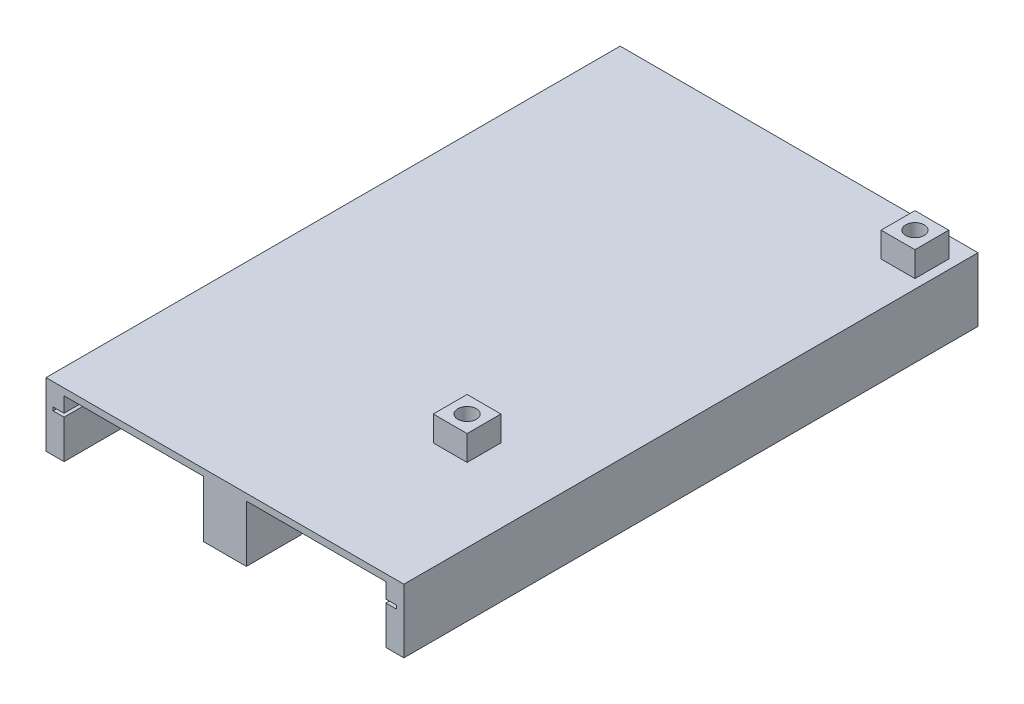
SolidWorks part; units mm, degrees
material "PLA"
ref_plane "Спереди" through (0, 0, 0) normal (0, 0, 1) x (1, 0, 0)
ref_plane "Сверху" through (0, 0, 0) normal (0, 1, 0) x (1, 0, 0)
ref_plane "Справа" through (0, 0, 0) normal (1, 0, 0) x (0, 0, -1)
sketch "Эскиз1" plane through (0, 0, 0) normal (0, 1, 0) x (1, 0, 0)
  line L0 (0, 0) -> (-4740.9496, 0) construction
  line L1 (0, 0) -> (0, -4740.9496) construction
  line L2 (35.675, 63.65) -> (39.675, 63.65)
  line L3 (-35.675, -63.65) -> (-39.675, -63.65)
  line L4 (-35.675, -63.65) -> (-35.675, 63.65)
  line L5 (-35.675, 63.65) -> (-39.675, 63.65)
  line L6 (-39.675, -63.65) -> (-39.675, 63.65)
  line L7 (-35.675, -63.65) -> (-39.675, 63.65) construction
  line L8 (-35.675, 63.65) -> (-39.675, -63.65) construction
  line L9 (39.675, -63.65) -> (39.675, 63.65)
  line L10 (35.675, -63.65) -> (39.675, -63.65)
  line L11 (35.675, -63.65) -> (35.675, 63.65)
  line L12 (35.675, 63.65) -> (39.675, -63.65) construction
  line L13 (35.675, -63.65) -> (39.675, 63.65) construction
  point P5 (-37.675, 0)
  point P14 (37.675, 0)
  dimension "D1" = 4
  dimension "D2" = 127.3
  dimension "D3" = 71.35
extrude "Бобышка-Вытянуть1" add sketch "Эскиз1" along normal blind 12.65
sketch "Эскиз2" plane through (0, 12.65, 0) normal (0, 1, 0) x (1, 0, 0)
  line L1 (39.675, 63.65) -> (-39.675, 63.65)
  line L2 (39.675, 63.65) -> (39.675, -63.65)
  line L3 (39.675, -63.65) -> (-39.675, -63.65)
  line L4 (-39.675, 63.65) -> (-39.675, -63.65)
extrude "Бобышка-Вытянуть2" add sketch "Эскиз2" along normal blind 1.5
sketch "Эскиз3" plane through (0, 0, -63.65) normal (0, 0, -1) x (-1, 0, 0)
  line L0 (0, 0) -> (0, 50000) construction
  line L1 (-35.675, 12.65) -> (-35.675, 0) construction
  line L2 (-35.675, 9.3) -> (-38.075, 9.3)
  line L3 (-35.675, 9.3) -> (-35.675, 8.55)
  line L4 (-35.675, 8.55) -> (-38.075, 8.55)
  line L5 (-38.075, 9.3) -> (-38.075, 8.55)
  line L6 (35.675, 8.55) -> (38.075, 8.55)
  line L7 (38.075, 9.3) -> (38.075, 8.55)
  line L8 (35.675, 9.3) -> (38.075, 9.3)
  line L9 (35.675, 9.3) -> (35.675, 8.55)
  line L10 (-39.675, 0) -> (-35.675, 0) construction
  dimension "D1" = 2.4
  dimension "D2" = 0.75
  dimension "D3" = 8.55
extrude "Вырез-Вытянуть1" cut sketch "Эскиз3" against normal through all from offset 1.5 offset against normal yes
sketch "Эскиз4" plane through (0, 12.65, 0) normal (0, -1, 0) x (1, 0, 0)
  line L0 (35.675, -63.65) -> (35.675, 63.65) construction
  line L1 (-35.675, -63.65) -> (35.675, -63.65)
  line L2 (-35.675, -63.65) -> (-35.675, -62.15)
  line L3 (-35.675, -62.15) -> (35.675, -62.15)
  line L4 (35.675, -63.65) -> (35.675, -62.15)
  dimension "D1" = 1.5
extrude "Бобышка-Вытянуть3" add sketch "Эскиз4" along normal up to surface (12.65 mm away) up to face at (37.675, 0, 0)
sketch "Эскиз6" plane through (0, 12.65, 0) normal (0, -1, 0) x (1, 0, 0)
  line L0 (35.675, -62.15) -> (35.675, 63.65) construction
  line L1 (32.325, -52.35) -> (24.825, -52.35)
  line L2 (32.325, -52.35) -> (32.325, -62.15)
  line L3 (32.325, -59.85) -> (24.825, -59.85) construction
  line L4 (24.825, -52.35) -> (24.825, -62.15)
  line L5 (32.325, -52.35) -> (24.825, -59.85) construction
  line L6 (32.325, -59.85) -> (24.825, -52.35) construction
  line L7 (35.675, -62.15) -> (-35.675, -62.15) construction
  line L8 (32.325, -62.15) -> (24.825, -62.15)
  circle A0 centre (28.575, -56.1) radius 2.1 construction
  point P0 (28.575, -56.1)
  dimension "D3" = 4.2
  dimension "D4" = 1.65
  dimension "D5" = 1.65
  dimension "D1" = 7.1
  dimension "D2" = 6.05
extrude "Бобышка-Вытянуть5" add sketch "Эскиз6" along normal blind 9.6
sketch "Эскиз7" plane through (0, 3.05, 0) normal (0, -1, 0) x (1, 0, 0)
  line L0 (24.825, -52.35) -> (32.325, -59.85) construction
  line L1 (32.325, -52.35) -> (24.825, -59.85) construction
  line L2 (32.325, -62.15) -> (32.325, -52.35) construction
  line L3 (24.825, -52.35) -> (24.825, -62.15) construction
  circle A0 centre (28.575, -56.1) radius 2.05
  dimension "D1" = 4.1
extrude "Вырез-Вытянуть2" cut sketch "Эскиз7" against normal blind 4.5
sketch "Эскиз8" plane through (0, 0, 0) normal (0, -1, 0) x (1, 0, 0)
  line L0 (-35.675, 63.65) -> (-35.675, -62.15) construction
  line L1 (-35.675, 38.05) -> (-38.075, 38.05)
  line L2 (-35.675, 38.05) -> (-35.675, 32.2)
  line L3 (-35.675, 32.2) -> (-38.075, 32.2)
  line L4 (-38.075, 38.05) -> (-38.075, 32.2)
  line L5 (0, 0) -> (0, 50000) construction
  line L6 (-35.675, -16.55) -> (-38.075, -16.55)
  line L7 (-35.675, -16.55) -> (-35.675, -22.4)
  line L8 (-35.675, -22.4) -> (-38.075, -22.4)
  line L9 (-38.075, -16.55) -> (-38.075, -22.4)
  line L10 (-39.675, 63.65) -> (-35.675, 63.65) construction
  line L11 (35.675, -22.4) -> (38.075, -22.4)
  line L12 (38.075, -16.55) -> (38.075, -22.4)
  line L13 (35.675, -16.55) -> (38.075, -16.55)
  line L14 (35.675, -16.55) -> (35.675, -22.4)
  line L15 (35.675, 32.2) -> (38.075, 32.2)
  line L16 (38.075, 38.05) -> (38.075, 32.2)
  line L17 (35.675, 38.05) -> (38.075, 38.05)
  line L18 (35.675, 38.05) -> (35.675, 32.2)
  line L19 (39.675, -63.65) -> (-39.675, -63.65) construction
  point P26 (0, -63.65)
  dimension "D1" = 2.4
  dimension "D2" = 5.85
  dimension "D3" = 48.75
  dimension "D4" = 25.6
extrude "Вырез-Вытянуть3" cut sketch "Эскиз8" against normal up to surface (8.55 mm away) up to face at (-36.875, 8.55, 0.75)
sketch "Эскиз10" plane through (0, 12.65, 0) normal (0, -1, 0) x (1, 0, 0)
  line L0 (-35.675, 63.65) -> (-35.675, -62.15) construction
  line L1 (-25.275, -51.75) -> (-28.275, -51.75)
  line L2 (-25.275, -51.75) -> (-25.275, -57.7)
  line L3 (-25.275, -57.7) -> (-28.275, -57.7)
  line L4 (-28.275, -51.75) -> (-28.275, -57.7)
  line L5 (24.825, -62.15) -> (-35.675, -62.15) construction
  line L6 (35.675, -62.15) -> (-35.675, -62.15) construction
  line L8 (15.225, -51.75) -> (18.225, -51.75)
  line L9 (15.225, -51.75) -> (15.225, -57.7)
  line L10 (15.225, -57.7) -> (18.225, -57.7)
  line L11 (18.225, -51.75) -> (18.225, -57.7)
  dimension "D1" = 10.4
  dimension "D2" = 4.45
  dimension "D3" = 10.4
  dimension "D4" = 3
  dimension "D5" = 50.9
extrude "Бобышка-Вытянуть6" add sketch "Эскиз10" along normal blind 3.95
sketch "Эскиз11" plane through (0, 12.65, 0) normal (0, -1, 0) x (1, 0, 0)
  line L1 (-25.275, -57.7) -> (15.225, -57.7)
  line L2 (-25.275, -57.7) -> (-25.275, -51.75)
  line L3 (-25.275, -51.75) -> (15.225, -51.75)
  line L4 (15.225, -57.7) -> (15.225, -51.75)
extrude "Бобышка-Вытянуть7" add sketch "Эскиз11" along normal blind 0.35
fillet "Скругление4" radius 4 1 edges at (-5.025, 12.65, -57.7)
fillet "Скругление5" radius 2 2 edges at (-26.775, 8.7, -57.7) (16.725, 8.7, -57.7)
sketch "Эскиз12" plane through (0, 0, -62.15) normal (0, 0, 1) x (1, 0, 0)
  line L0 (24.825, 12.65) -> (-35.675, 12.65) construction
  line L1 (15.475, 8) -> (-25.525, 8)
  line L2 (15.475, 8) -> (15.475, 12.65)
  line L12 (15.475, 12.65) -> (-25.525, 12.65)
  line L13 (-25.525, 8) -> (-25.525, 12.65)
  line L15 (-5.025, 12.3) -> (-5.025, 12.65) construction
  line L17 (-25.275, 12.3) -> (15.225, 12.3) construction
  point P13 (-5.025, 12.3)
  dimension "D1" = 4.65
  dimension "D2" = 41
extrude "Вырез-Вытянуть4" cut sketch "Эскиз12" against normal through all
sketch "Эскиз13" plane through (0, 12.65, 0) normal (0, -1, 0) x (1, 0, 0)
  line L0 (0, 63.65) -> (0, 50063.65) construction
  line L1 (-35.675, 63.65) -> (35.675, 63.65) construction
  line L2 (-4.75, 60.9) -> (-4.75, 63.65)
  line L3 (4.75, 60.9) -> (-4.75, 60.9) construction
  line L4 (4.75, 60.9) -> (4.75, 51.4)
  line L5 (4.75, 51.4) -> (-4.75, 51.4)
  line L6 (-4.75, 60.9) -> (-4.75, 51.4)
  line L7 (4.75, 60.9) -> (-4.75, 51.4) construction
  line L8 (4.75, 51.4) -> (-4.75, 60.9) construction
  line L9 (-4.75, 63.65) -> (4.75, 63.65)
  line L10 (4.75, 63.65) -> (4.75, 60.9)
  circle A0 centre (0, 56.15) radius 2.75 construction
  point P4 (0, 63.65)
  point P5 (0, 56.15)
  dimension "D1" = 5.5
  dimension "D2" = 9.5
  dimension "D3" = 7.5
extrude "Бобышка-Вытянуть8" add sketch "Эскиз13" along normal blind 12.55
sketch "Эскиз14" plane through (0, 0.1, 0) normal (0, -1, 0) x (1, 0, 0)
  line L0 (-4.75, 60.9) -> (4.75, 51.4) construction
  line L1 (4.75, 60.9) -> (-4.75, 51.4) construction
  line L2 (4.75, 51.4) -> (4.75, 63.65) construction
  line L3 (-4.75, 63.65) -> (-4.75, 51.4) construction
  line L4 (-4.75, 60.9) -> (4.75, 60.9) construction
  circle A0 centre (0, 56.15) radius 1.6
  dimension "D1" = 3.2
extrude "Вырез-Вытянуть5" cut sketch "Эскиз14" against normal blind 7
sketch "Эскиз15" plane through (0, 14.15, 0) normal (0, 1, 0) x (1, 0, 0)
  line L0 (39.675, -63.65) -> (39.675, 63.65) construction
  line L1 (30.1454, 59.1971) -> (37.6454, 59.1971)
  line L2 (30.1454, 59.1971) -> (30.1454, 51.6971)
  line L3 (30.1454, 51.6971) -> (37.6454, 51.6971)
  line L4 (37.6454, 59.1971) -> (37.6454, 51.6971)
  line L5 (30.1454, 59.1971) -> (37.6454, 51.6971) construction
  line L6 (30.1454, 51.6971) -> (37.6454, 59.1971) construction
  line L7 (15.8005, -25.7612) -> (23.3005, -25.7612)
  line L8 (15.8005, -25.7612) -> (15.8005, -33.2612)
  line L9 (15.8005, -33.2612) -> (23.3005, -33.2612)
  line L10 (23.3005, -25.7612) -> (23.3005, -33.2612)
  line L11 (15.8005, -25.7612) -> (23.3005, -33.2612) construction
  line L12 (15.8005, -33.2612) -> (23.3005, -25.7612) construction
  line L13 (-39.675, -63.65) -> (39.675, -63.65) construction
  point P0 (33.8954, 55.4471)
  point P5 (19.5505, -29.5112)
  dimension "D1" = 7.5
  dimension "D2" = 20.1245
  dimension "D3" = 34.1388
  dimension "D4" = 5.7796
  dimension "D5" = 119.0971
extrude "Бобышка-Вытянуть9" add sketch "Эскиз15" along normal blind 5.55
chamfer "Фаска1" distance 0.45 angle 45 1 edges at (0, 0.1, 54.55)
sketch "Эскиз16" plane through (0, 19.7, 0) normal (0, 1, 0) x (1, 0, 0)
  line L0 (30.1454, 59.1971) -> (37.6454, 51.6971) construction
  line L1 (37.6454, 59.1971) -> (30.1454, 51.6971) construction
  line L2 (23.3005, -25.7612) -> (15.8005, -33.2612) construction
  line L3 (15.8005, -25.7612) -> (23.3005, -33.2612) construction
  circle A0 centre (19.5505, -29.5112) radius 2.05
  circle A1 centre (33.8954, 55.4471) radius 2.05
  dimension "D1" = 4.1
extrude "Вырез-Вытянуть6" cut sketch "Эскиз16" against normal blind 5
